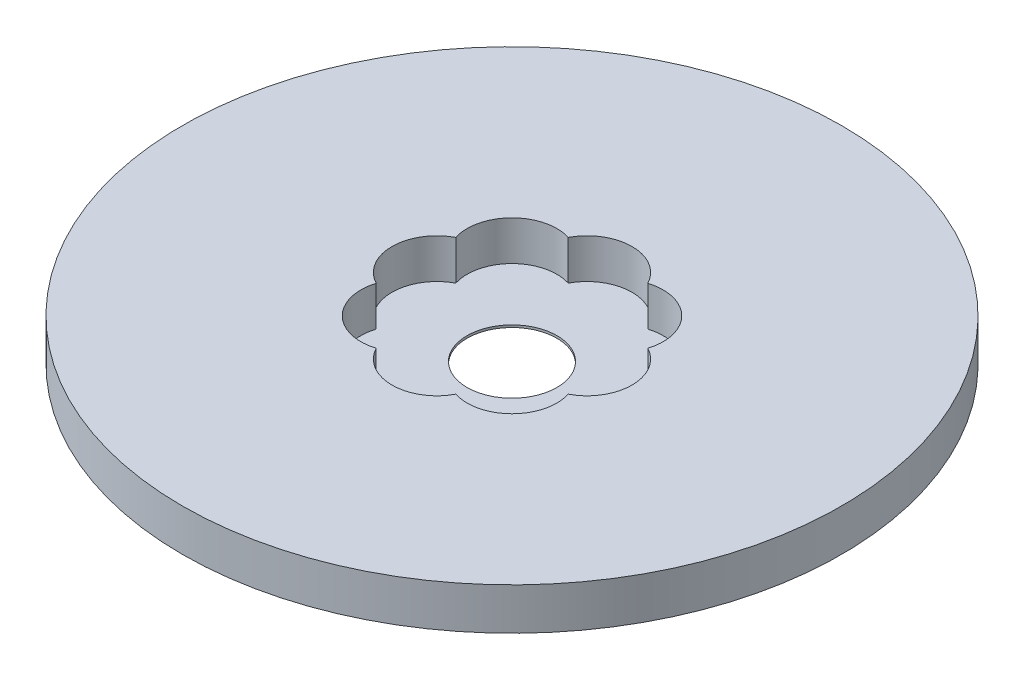
SolidWorks part; units mm, degrees
ref_plane "Front Plane" through (0, 0, 0) normal (0, 0, 1) x (1, 0, 0)
ref_plane "Top Plane" through (0, 0, 0) normal (0, 1, 0) x (1, 0, 0)
ref_plane "Right Plane" through (0, 0, 0) normal (1, 0, 0) x (0, 0, -1)
sketch "Sketch1" plane through (0, 0, 0) normal (0, 1, 0) x (1, 0, 0)
  circle A0 centre (0, 0) radius 55
  dimension "FLANGE_OD" = 110
extrude "Boss-Extrude1" add sketch "Sketch1" along normal blind 7
sketch "Sketch2" plane through (0, 0, 0) normal (0, 1, 0) x (1, 0, 0)
  circle A0 centre (0, 0) radius 7.5
  dimension "BORE_D" = 15
extrude "Cut-Extrude1" cut sketch "Sketch2" along normal through all
sketch "Sketch3" plane through (0, 7, 0) normal (0, 1, 0) x (1, 0, 0)
  circle A0 centre (0, 0) radius 12.5338 construction
  circle A1 centre (-12.5338, 0) radius 7.4984
  dimension "BOLT_D" = 14.9969
  dimension "BOLT_PCD" = 25.0677
extrude "Cut-Extrude2" cut sketch "Sketch3" against normal blind 6.6138
pattern_circular "CirPattern1" count 8 over 360 about axis through (0, 0, 0) along (0, 1, 0) of "Cut-Extrude2"
